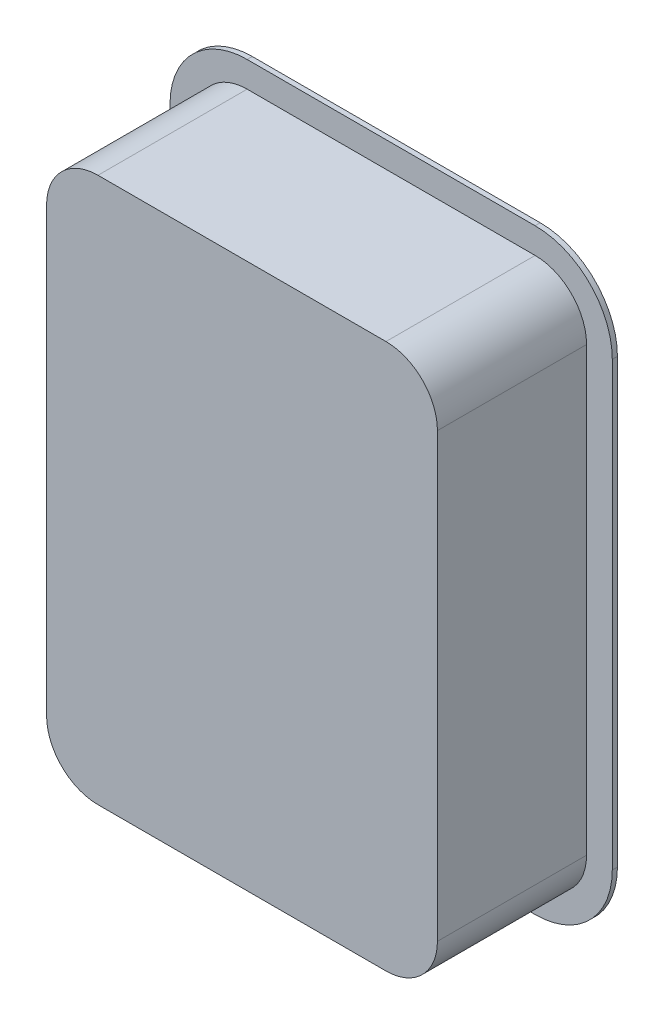
SolidWorks part; units mm, degrees
ref_plane "Front Plane" through (0, 0, 0) normal (0, 0, 1) x (1, 0, 0)
ref_plane "Top Plane" through (0, 0, 0) normal (0, 1, 0) x (1, 0, 0)
ref_plane "Right Plane" through (0, 0, 0) normal (1, 0, 0) x (0, 0, -1)
sketch "Sketch1" plane through (0, 0, 0) normal (0, 0, 1) x (1, 0, 0)
  line L1 (10, 0) -> (66, 0)
  line L2 (0, 10) -> (0, 96)
  line L3 (10, 106) -> (66, 106)
  line L4 (76, 10) -> (76, 96)
  arc A0 (10, 0) -> (0, 10) centre (10, 10) cw
  arc A1 (66, 0) -> (76, 10) centre (66, 10) ccw
  arc A2 (66, 106) -> (76, 96) centre (66, 96) cw
  arc A3 (0, 96) -> (10, 106) centre (10, 96) cw
  point P7 (0, 0)
  point P12 (76, 106)
  point P15 (0, 106)
  dimension "D3" = 10
  dimension "D1" = 106
  dimension "D2" = 76
extrude "Boss-Extrude1" add sketch "Sketch1" along normal blind 30
shell "Shell1" thickness 3 removed face at (38, 53, 0)
sketch "Sketch2" plane through (0, 0, 0) normal (0, 0, -1) x (-1, 0, 0)
  line L0 (5, 10) -> (5, 96)
  line L1 (-10, 111) -> (-66, 111)
  line L2 (-81, 96) -> (-81, 10)
  line L3 (-66, -5) -> (-10, -5)
  line L4 (0, 10) -> (0, 96)
  line L5 (-10, 106) -> (-66, 106)
  line L6 (-76, 96) -> (-76, 10)
  line L7 (-66, 0) -> (-10, 0)
  line L8 (0, 10) -> (0, 96)
  line L9 (-10, 106) -> (-66, 106)
  line L10 (-76, 96) -> (-76, 10)
  line L11 (-66, 0) -> (-10, 0)
  arc A0 (-10, -5) -> (5, 10) centre (-10, 10) ccw
  arc A1 (5, 96) -> (-10, 111) centre (-10, 96) ccw
  arc A2 (-66, 111) -> (-81, 96) centre (-66, 96) ccw
  arc A3 (-81, 10) -> (-66, -5) centre (-66, 10) ccw
  arc A4 (-10, 0) -> (0, 10) centre (-10, 10) ccw
  arc A5 (0, 96) -> (-10, 106) centre (-10, 96) ccw
  arc A6 (-66, 106) -> (-76, 96) centre (-66, 96) ccw
  arc A7 (-76, 10) -> (-66, 0) centre (-66, 10) ccw
  arc A8 (-10, 0) -> (0, 10) centre (-10, 10) ccw
  arc A9 (0, 96) -> (-10, 106) centre (-10, 96) ccw
  arc A10 (-66, 106) -> (-76, 96) centre (-66, 96) ccw
  arc A11 (-76, 10) -> (-66, 0) centre (-66, 10) ccw
  dimension "D1" = 0
  dimension "D2" = 5
extrude "Boss-Extrude2" add sketch "Sketch2" against normal blind 1
sketch "Sketch3" plane through (73, 0, 0) normal (-1, 0, 0) x (0, 0, 1)
  line L0 (0, 10) -> (0, 96) construction
  line L1 (10, 80.7939) -> (12.313, 80.7939)
  line L2 (10, 80.7939) -> (10, 66.1452)
  line L3 (10, 66.1452) -> (12.313, 66.1452)
  line L4 (12.313, 80.7939) -> (12.313, 66.1452)
  line L5 (10, 42.4113) -> (12.313, 42.4113)
  line L6 (10, 42.4113) -> (10, 27.7627)
  line L7 (10, 27.7627) -> (12.313, 27.7627)
  line L8 (12.313, 42.4113) -> (12.313, 27.7627)
  dimension "D1" = 10
extrude "Boss-Extrude3" add sketch "Sketch3" along normal blind 6
sketch "Sketch4" plane through (0, 0, 10) normal (0, 0, -1) x (-1, 0, 0)
  line L0 (-70, 95) -> (-70, 11)
  line L1 (-65, 6) -> (-23, 6)
  line L2 (-18.5279, 13.2361) -> (-60.5279, 97.2361)
  line L3 (-10, 3) -> (-66, 3) construction
  line L4 (-73, 10) -> (-73, 96) construction
  line L5 (-66, 103) -> (-10, 103) construction
  line L7 (-3, 96) -> (-3, 10) construction
  arc A0 (-70, 95) -> (-60.5279, 97.2361) centre (-65, 95) cw
  arc A1 (-23, 6) -> (-18.5279, 13.2361) centre (-23, 11) ccw
  arc A2 (-70, 11) -> (-65, 6) centre (-65, 11) ccw
  point P3 (-70.147, 106.6066)
  point P10 (-63.3008, 92.886)
  point P11 (-13.9284, 7.017)
  dimension "D1" = 5
  dimension "D4" = 8
  dimension "D2" = 3
  dimension "D3" = 3
  dimension "D5" = 20
extrude "Boss-Extrude4" add sketch "Sketch4" along normal blind 10
fillet "Fillet1" radius 10 8 edges at (70.9497, 100.9497, 27) (73, 53, 27) (70.9497, 5.0503, 27) (38, 3, 27) (5.0503, 5.0503, 27) (3, 53, 27) (5.0503, 100.9497, 27) (38, 103, 27)
fillet "Fillet2" radius 3 21 edges at (70, 19.3813, 10) (68.5355, 7.4645, 10) (44, 6, 10) (18.7467, 8.3713, 10) (70, 87.897, 10) (66.1488, 99.8662, 10) (70.9497, 100.9497, 0) (73, 53, 0) (70.9497, 5.0503, 0) (38, 3, 0) (5.0503, 5.0503, 0) (3, 53, 0) (5.0503, 100.9497, 0) (39.5279, 55.2361, 0) (18.7467, 8.3713, 0) (44, 6, 0) (68.5355, 7.4645, 0) (70, 53, 0) (66.1488, 99.8662, 0) (39.5279, 55.2361, 10) (38, 103, 0)
